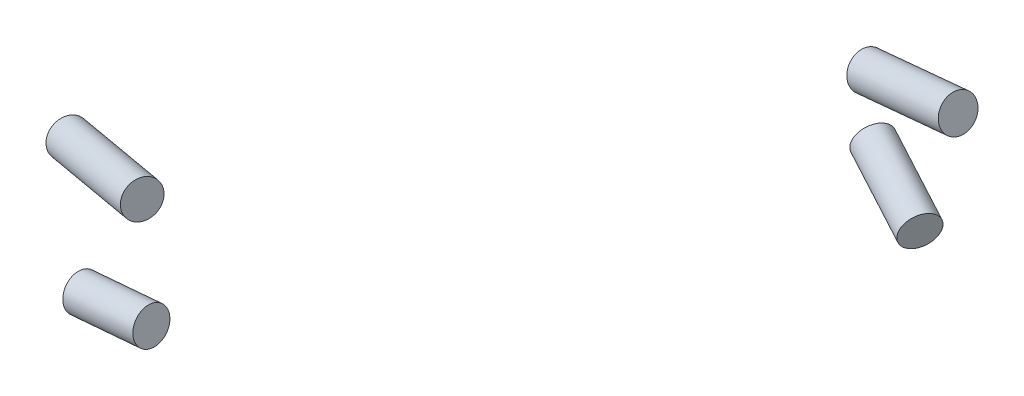
SolidWorks part; units mm, degrees
ref_plane "Plano frontal" through (0, 0, 0) normal (0, 0, 1) x (1, 0, 0)
ref_plane "Plano superior" through (0, 0, 0) normal (0, 1, 0) x (1, 0, 0)
ref_plane "Plano direito" through (0, 0, 0) normal (1, 0, 0) x (0, 0, -1)
sketch3d "SUSP_FL_rocker_bracket_a_eixo"
  line L0 (-253.1609, 3.0606, -245.1125) -> (-282.5474, -0.7335, -246.5681)
sweep "SUSP_FL_rocker_bracket_a" add path "SUSP_FL_rocker_bracket_a_eixo" circular profile diameter 14 parameters "D3"=14
sketch3d "SUSP_FL_rocker_bracket_b_eixo"
  line L0 (-258.3043, 43.4709, -246.6084) -> (-300.1526, 37.6935, -258.7919)
sweep "SUSP_FL_rocker_bracket_b" add path "SUSP_FL_rocker_bracket_b_eixo" circular profile diameter 14 parameters "D3"=14
sketch3d "SUSP_FL_coilover_bracket_a_eixo"
  line L0 (-166.0262, -30.2321, -464.3188) -> (-198.5574, -22.1626, -478.0795)
sweep "SUSP_FL_coilover_bracket_a" add path "SUSP_FL_coilover_bracket_a_eixo" circular profile diameter 14 parameters "D3"=14
sketch3d "SUSP_FL_coilover_bracket_b_eixo"
  line L0 (-164.8059, 4.0474, -478.3248) -> (-206.5598, -4.6958, -483.6357)
sweep "SUSP_FL_coilover_bracket_b" add path "SUSP_FL_coilover_bracket_b_eixo" circular profile diameter 14 parameters "D3"=14
sketch3d "REF_SKETCH"
  line L0 (-259, -223.87, -256.303) -> (-251, -219.07, -252.703)
  line L1 (-252.6, -224.47, -257.703) -> (-257.4, -218.47, -251.303)
  line L2 (-255, -221.47, -254.503) -> (-255, -14.5, -244.753)
  line L3 (-209, -243.24, -44.183) -> (-201, -238.44, -40.583)
  line L4 (-202.6, -243.84, -45.583) -> (-207.4, -237.84, -39.183)
  line L5 (-205, -240.84, -42.383) -> (-205, 0, -42.383)
  line L6 (-274, -92.8, -84.1915) -> (-266, -88, -80.5915)
  line L7 (-267.6, -93.4, -85.5915) -> (-272.4, -87.4, -79.1915)
  line L8 (-295.35, 16.08, -254.48) -> (-287.35, 20.88, -250.88)
  line L9 (-288.95, 15.48, -255.88) -> (-293.75, 21.48, -249.48)
  line L10 (-303.3536, 44.6802, -261.0144) -> (-279.3464, -7.7202, -244.3456)
  line L11 (-206.5586, -15.8292, -482.6576) -> (-198.5586, -11.0292, -479.0576)
  line L12 (-200.1586, -16.4292, -484.0576) -> (-204.9586, -10.4292, -477.6576)
ref_point "P_UCA_IN_FRONT"
ref_axis "A_UCA_PIVOT" through (-255, -221.47, -254.503) along (0, 0.9989, 0.0471)
ref_point "P_LCA_IN_FRONT"
ref_axis "A_LCA_PIVOT" through (-205, -240.84, -42.383) along (0, 1, 0)
ref_point "P_TIE_ROD_IN"
ref_point "P_ROCKER_PIVOT"
ref_axis "A_ROCKER" through (-303.3536, 44.6802, -261.0144) along (0.4001, -0.8733, 0.2778)
ref_point "P_DAMPER_CHASSIS"
